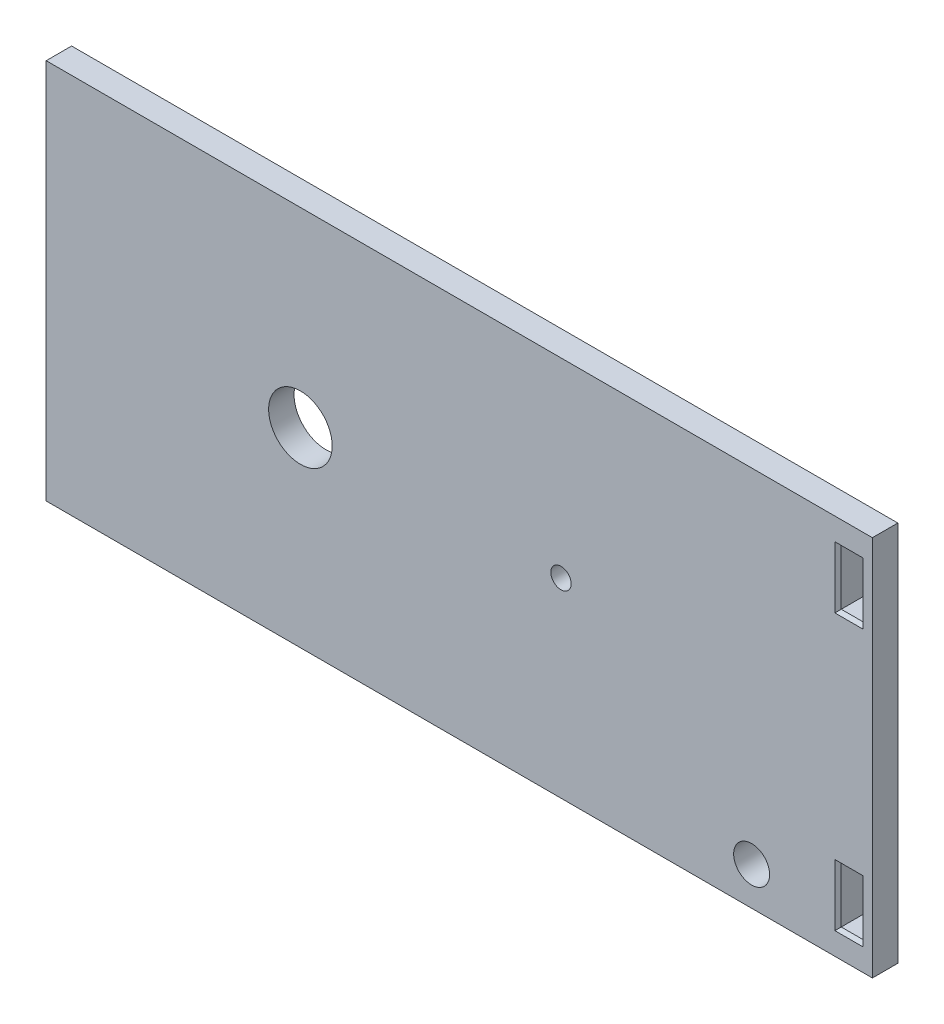
SolidWorks part; units mm, degrees
ref_plane "Front Plane" through (0, 0, 0) normal (0, 0, 1) x (1, 0, 0)
ref_plane "Top Plane" through (0, 0, 0) normal (0, 1, 0) x (1, 0, 0)
ref_plane "Right Plane" through (0, 0, 0) normal (1, 0, 0) x (0, 0, -1)
sketch "Sketch1" plane through (0, 0, 0) normal (0, 0, 1) x (1, 0, 0)
  line L2 (-65, -30) -> (-65, 30)
  line L12 (61.3, 26) -> (61.3, 17.3) construction
  line L13 (-65, 30) -> (65, 30)
  line L15 (-65, -30) -> (65, -30)
  line L16 (65, 30) -> (65, -30)
  line L17 (59.6, 26) -> (63, 26)
  line L18 (59.6, 26) -> (59.6, 17.3)
  line L19 (59.6, 17.3) -> (63, 17.3)
  line L20 (63, 26) -> (63, 17.3)
  line L21 (59.6, -17.3) -> (63, -17.3)
  line L22 (59.6, -17.3) -> (59.6, -26)
  line L23 (59.6, -26) -> (63, -26)
  line L24 (63, -17.3) -> (63, -26)
  line L25 (61.3, -17.3) -> (61.3, -26) construction
  line L26 (63, 21.65) -> (59.6, 21.65) construction
  line L27 (63, -21.65) -> (59.6, -21.65) construction
  circle A3 centre (-25, 0) radius 5
  circle A4 centre (46, -24) radius 2.83
  circle A6 centre (16, 0) radius 1.6
  point P2 (0, 30)
  point P9 (65, 0)
  point P27 (0, 0)
  dimension "D6" = 10
  dimension "D4" = 5.66
  dimension "D2" = 60
  dimension "D3" = 130
  dimension "D8" = 24
  dimension "D1" = 8.7
  dimension "D9" = 3.4
  dimension "D10" = 21.65
  dimension "D11" = 21.65
  dimension "D5" = 40
  dimension "D7" = 86.3
  dimension "D12" = 71
  dimension "D13" = 41
extrude "Boss-Extrude1" add sketch "Sketch1" along normal mid plane 4
chamfer "Chamfer1" distance 0.5 angle 45 8 edges at (61.3, 17.3, 2) (59.6, 21.65, 2) (61.3, 26, 2) (63, 21.65, 2) (61.3, -26, 2) (59.6, -21.65, 2) (61.3, -17.3, 2) (63, -21.65, 2)
sketch "Sketch3" plane through (0, 0, -2) normal (0, 0, -1) x (-1, 0, 0)
  line L0 (-61.3, 26) -> (-61.3, 17.3) construction
  line L1 (-63, 21.65) -> (-59.6, 21.65) construction
  line L2 (-61.3, -17.3) -> (-61.3, -26) construction
  line L3 (-59.6, -17.3) -> (-63, -17.3) construction
  line L4 (-63, -21.65) -> (-59.6, -21.65) construction
equation "\"hole_width\"=3.4"
equation "\"hole_length\"=8.7"
equation "\"pin_hole_height\"=8.7"
equation "\"D1@Sketch1\"=\"pin_hole_height\""
equation "\"pin_hole_width\"=3.4"
equation "\"D9@Sketch1\"=\"pin_hole_width\""
equation "\"wall_thick_ness\"=4"
equation "\"D1@Boss-Extrude1\"=\"wall_thick_ness\""
equation "\"back_boost\"= 7"
equation "\"D5@Sketch1\"=\"back_boost\"+33.00mm"
equation "\"D3@Sketch1\"=123.00mm+\"back_boost\""
